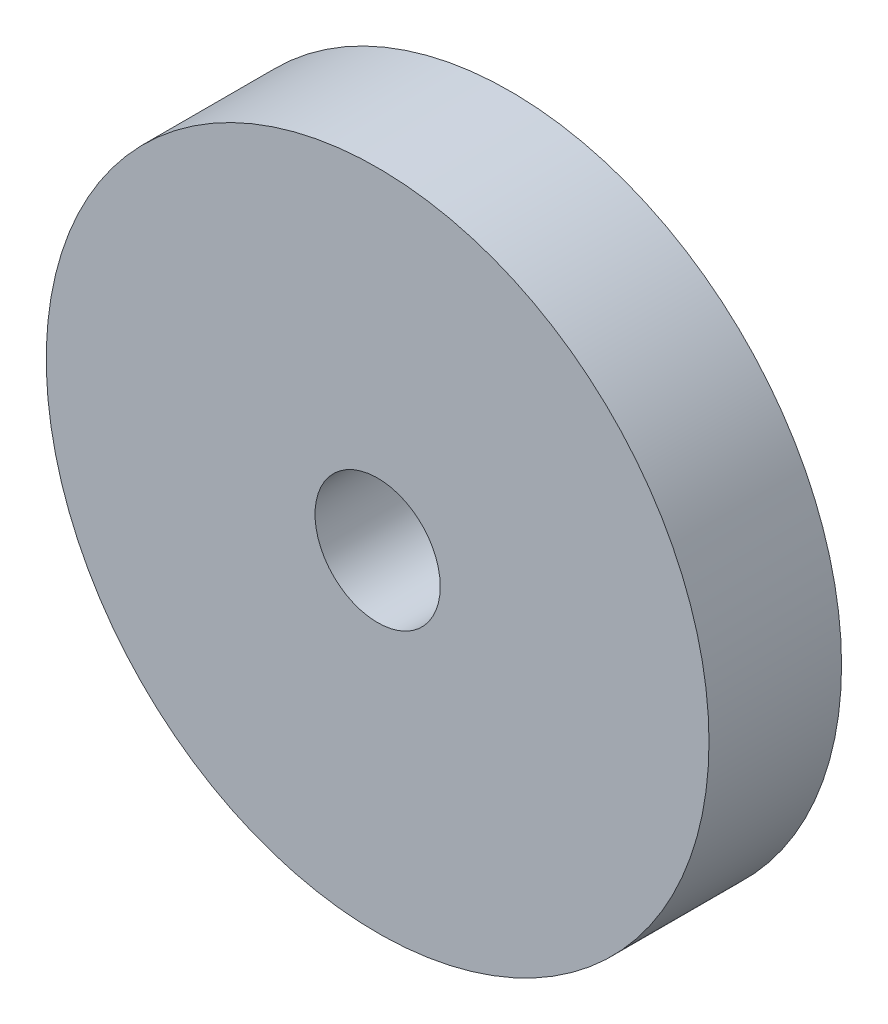
SolidWorks part; units mm, degrees
ref_plane "Front Plane" through (0, 0, 0) normal (0, 0, 1) x (1, 0, 0)
ref_plane "Top Plane" through (0, 0, 0) normal (0, 1, 0) x (1, 0, 0)
ref_plane "Right Plane" through (0, 0, 0) normal (1, 0, 0) x (0, 0, -1)
sketch "Sketch1" plane through (0, 0, 0) normal (0, 0, 1) x (1, 0, 0)
  circle A0 centre (0, 0) radius 7.9375
  circle A1 centre (0, 0) radius 1.5
  dimension "D1" = 15.875
  dimension "D2" = 3
extrude "Boss-Extrude1" add sketch "Sketch1" along normal blind 3.175 contours A1 | A0 region at (0, 0, 0)
equation "\"m\"= 2.28833"
